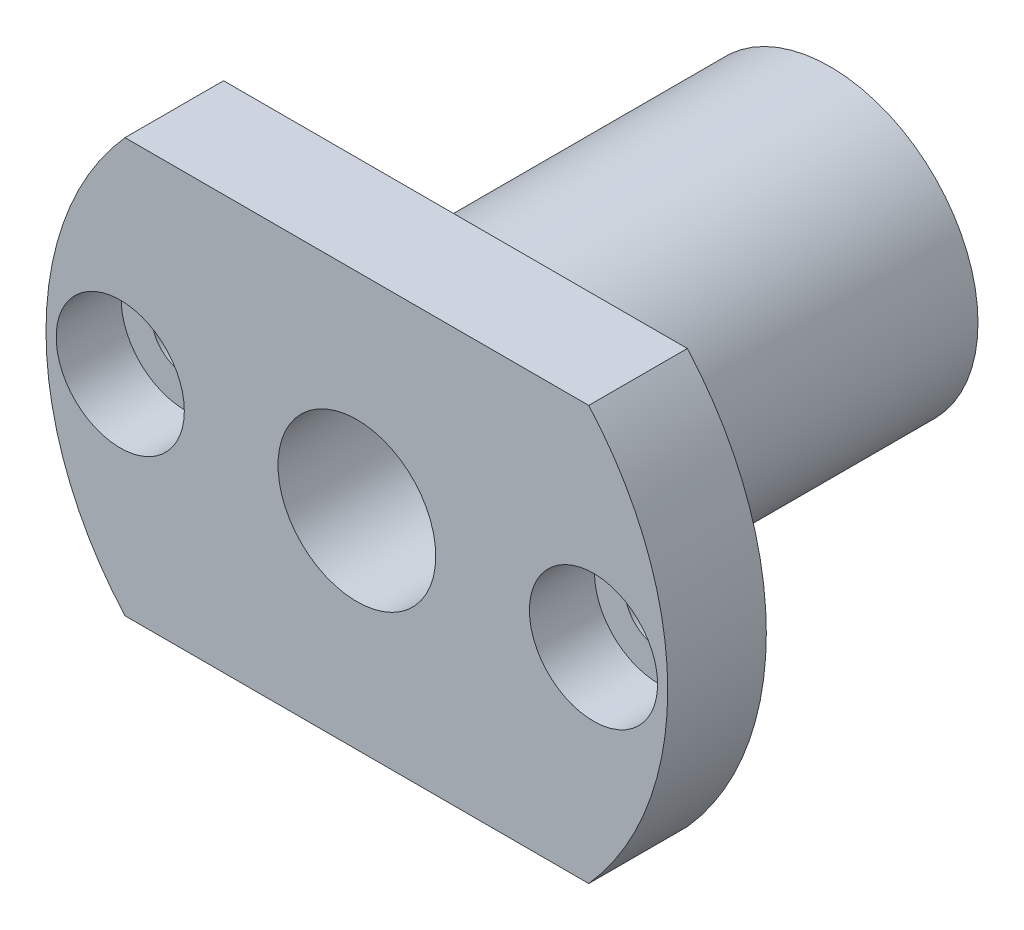
SolidWorks part; units mm, degrees
ref_plane "Front Plane" through (0, 0, 0) normal (0, 0, 1) x (1, 0, 0)
ref_plane "Top Plane" through (0, 0, 0) normal (0, 1, 0) x (1, 0, 0)
ref_plane "Right Plane" through (0, 0, 0) normal (1, 0, 0) x (0, 0, -1)
sketch "Sketch1" plane through (0, 0, 0) normal (0, 0, 1) x (1, 0, 0)
  line L0 (-24.1912, 0) -> (23.9975, 0) construction
  line L1 (0, 14.7953) -> (0, -16.1499) construction
  line L2 (-11.7601, 10.5) -> (11.7601, 10.5)
  line L3 (-11.7601, -10.5) -> (11.7601, -10.5)
  arc A0 (-11.7601, 10.5) -> (-11.7601, -10.5) centre (0, 0) ccw
  arc A1 (11.7601, -10.5) -> (11.7601, 10.5) centre (0, 0) ccw
  circle A2 centre (0, 0) radius 4
  circle A3 centre (0, 0) radius 7.5
  circle A4 centre (-12, 0) radius 1.7
  circle A5 centre (12, 0) radius 1.7
  dimension "D1" = 21
  dimension "D2" = 12
extrude "Boss-Extrude1" add sketch "Sketch1" along normal blind 5 separate body contours L3 A1 L2 A0 A3 A4 A5 | A3 A2 region at (0, 10.1212, 0) region at (-7.2879, 0, 0)
extrude "Boss-Extrude2" add sketch "Sketch1<3>" against normal blind 19 contours A3 A2 region at (-7.2879, 0, 0)
sketch "Sketch1<3>" plane through (0, 0, 0) normal (0, 0, 1) x (1, 0, 0) same geometry as "Sketch1"
sketch "Sketch2" plane through (0, 0, 5) normal (0, 0, 1) x (1, 0, 0)
  line L0 (-14.7434, 0) -> (-6.4329, 0) construction
  line L1 (-12, -2.3272) -> (-12, 2.7714) construction
  line L2 (0, 6.6097) -> (0, -6.3317) construction
  circle A0 centre (-12, 0) radius 3.25
  circle A1 centre (12, 0) radius 3.25
extrude "Cut-Extrude1" cut sketch "Sketch2" against normal blind 3.3
